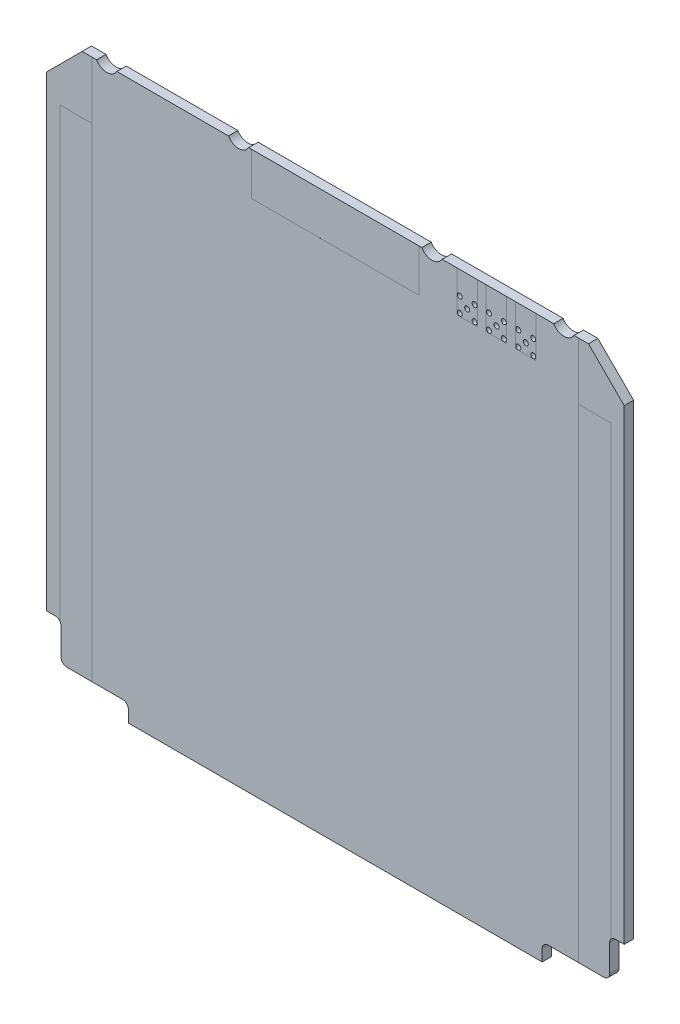
SolidWorks part; units mm, degrees
material "FR4_stuffedProtoboard"
ref_plane "Front Plane" through (0, 0, 0) normal (0, 0, 1) x (1, 0, 0)
ref_plane "Top Plane" through (0, 0, 0) normal (0, 1, 0) x (1, 0, 0)
ref_plane "Right Plane" through (0, 0, 0) normal (1, 0, 0) x (0, 0, -1)
ref_plane "Plane4" through (0, 0, -0.0125) normal (0, 0, -1) x (-1, 0, 0)
sketch "Sketch1" plane through (0, 0, -0.0125) normal (0, 0, -1) x (-1, 0, 0)
  line L4 (49.3, -50) -> (49.3, 45.3)
  line L6 (49.3, 45.3) -> (-49.3, 45.3)
  line L12 (-49.3, 45.3) -> (-49.3, -50)
  line L17 (-49.3, -50) -> (49.3, -50)
  line L18 (0, -50) -> (0, 45.3) construction
  dimension "D7" = 95.3
  dimension "D1" = 98.6
  dimension "D34" = 50
extrude "basicSize" add sketch "Sketch1" against normal blind 1.6
chamfer "Chamfer1" distance 6.1 angle 45 2 edges at (49.3, 45.3, 0.7875) (-49.3, 45.3, 0.7875)
sketch "Sketch4" plane through (0, 0, 1.5875) normal (0, 0, 1) x (1, 0, 0)
  line L1 (37.2679, 45.3) -> (40.7321, 45.3)
  line L7 (-43.2, 45.3) -> (43.2, 45.3) construction
  line L8 (49.3, 39.2) -> (49.3, -50) construction
  arc A0 (40.7321, 45.3) -> (37.2679, 45.3) centre (39, 46.3) cw
  point P5 (39, 44.3)
  dimension "D1" = 2
  dimension "D3" = 10.3
  dimension "D2" = 1
extrude "backplaneSideScrewCutout" cut sketch "Sketch4" against normal through all both and the other way through all
pattern_linear "LPattern3" count 2 spacing 22.5 along (-1, 0, 0) of "backplaneSideScrewCutout"
mirror "Mirror3" about plane through (0, 0, 0) normal (1, 0, 0) of "LPattern3"
sketch "Sketch6" plane through (0, 0, 1.5875) normal (0, 0, 1) x (1, 0, 0)
  line L0 (-49.3, -50) -> (-49.3, 39.2) construction
  line L1 (-49.3, -40.4) -> (-46.8, -40.4)
  line L2 (-49.3, -40.4) -> (-49.3, -50)
  line L4 (-46.8, -40.4) -> (-46.8, -47)
  line L5 (49.3, -50) -> (-49.3, -50) construction
  line L6 (-35.3, -50) -> (-49.3, -50)
  line L7 (-35.3, -50) -> (-35.3, -47)
  line L8 (-35.3, -47) -> (-46.8, -47)
  dimension "D1" = 2.5
  dimension "D2" = 3
  dimension "D3" = 9.6
  dimension "D4" = 14
extrude "Cut-Extrude4" cut sketch "Sketch6" against normal through all
fillet "Fillet1" radius 1 3 edges at (-35.3, -47, 0.7875) (-46.8, -47, 0.7875) (-46.8, -40.4, 0.7875)
mirror "Mirror1" about plane through (0, 0, 0) normal (1, 0, 0) of "Cut-Extrude4", "Fillet1"
sketch "Sketch5" plane through (0, 0, 1.5875) normal (0, 0, 1) x (1, 0, 0)
  line L0 (21.23, 41.37) -> (23.77, 38.83) construction
  line L1 (21.23, 38.83) -> (21.23, 41.37) construction
  line L2 (21.23, 41.37) -> (23.77, 41.37) construction
  line L4 (49.3, 39.2) -> (49.3, -40.4) construction
  line L5 (-14.7679, 45.3) -> (14.7679, 45.3) construction
  circle A0 centre (22.5, 40.1) radius 0.425
  circle A1 centre (21.23, 41.37) radius 0.425
  circle A3 centre (21.23, 38.83) radius 0.425
  circle A4 centre (23.77, 41.37) radius 0.425
  circle A5 centre (23.77, 38.83) radius 0.425
  dimension "D2" = 0.85
  dimension "D1" = 2.54
  dimension "D3" = 3.93
  dimension "D4" = 28.07
extrude "Cut-Extrude3" cut sketch "Sketch5" against normal through all
pattern_linear "LPattern2" count 3 spacing 5 along (1, 0, 0) of "Cut-Extrude3"
sketch "partFootprints" plane through (0, 0, 1.5875) normal (0, 0, 1) x (1, 0, 0)
  line L1 (18.2321, 45.3) -> (37.2679, 45.3) construction
  line L6 (20.75, 45.3) -> (20.75, 38.35)
  line L7 (20.75, 38.35) -> (24.25, 38.35)
  line L8 (24.25, 38.35) -> (24.25, 45.3)
  line L9 (24.25, 45.3) -> (20.75, 45.3)
  line L10 (25.75, 45.3) -> (25.75, 38.35)
  line L11 (25.75, 38.35) -> (29.25, 38.35)
  line L12 (29.25, 38.35) -> (29.25, 45.3)
  line L13 (29.25, 45.3) -> (25.75, 45.3)
  line L14 (30.75, 45.3) -> (30.75, 38.35)
  line L15 (30.75, 38.35) -> (34.25, 38.35)
  line L16 (34.25, 38.35) -> (34.25, 45.3)
  line L17 (34.25, 45.3) -> (30.75, 45.3)
  line L19 (32.5, 38.35) -> (32.5, 40.1) construction
  line L23 (22.5, 38.35) -> (22.5, 40.1) construction
  circle A2 centre (22.5, 40.1) radius 0.425 construction
  circle A5 centre (32.5, 40.1) radius 0.425 construction
  dimension "D1" = 1.75
  dimension "D8" = 3.5
  dimension "D6" = 3
extrude "MMCXfootprint" cut sketch "partFootprints" against normal blind 0.0001
sketch "Sketch7" plane through (0, 0, 1.5875) normal (0, 0, 1) x (1, 0, 0)
  line L0 (-14.2875, 45.5) -> (-14.2875, 39.912) construction
  line L1 (-14.2875, 45.3) -> (-14.2875, 38.007)
  line L2 (-12.2428, 38.007) -> (-11.8872, 38.007) construction
  line L3 (-14.2875, 38.007) -> (14.2875, 38.007)
  line L4 (14.2875, 45.5) -> (14.2875, 39.912) construction
  line L5 (14.2875, 45.3) -> (14.2875, 38.007)
  line L7 (-14.7679, 45.3) -> (14.7679, 45.3) construction
  line L8 (-14.2875, 45.3) -> (14.2875, 45.3)
extrude "TigerEyeFootprint" cut sketch "Sketch7" against normal blind 0.0001
sketch "thermalContacts_upper" plane through (0, 0, 1.5875) normal (0, 0, 1) x (1, 0, 0)
  line L0 (-49.3, -40.4) -> (-49.3, 39.2) construction
  line L1 (35.3, -50) -> (-35.3, -50) construction
  line L2 (-49.3, 45.3) -> (49.3, 45.3) construction
  line L3 (-47, 35.5) -> (-47, -41.5)
  line L5 (-41.5, 35.5) -> (-47, 35.5)
  line L18 (-41.5, 35.5) -> (-41.5, 47)
  line L23 (-41.5, 47) -> (-56.1922, 47)
  line L24 (-56.1922, 47) -> (-56.1922, -41.5)
  line L25 (-56.1922, -41.5) -> (-47, -41.5)
  dimension "D1" = 2.3
  dimension "D2" = 8.5
  dimension "D3" = 9.8
  dimension "D4" = 7.8
  dimension "D5" = 88.5
  dimension "D6" = 14.6922
extrude "keepOut_bottom" cut sketch "thermalContacts_upper" against normal blind 0.0001
sketch "Sketch3" plane through (0, 0, 1.5875) normal (0, 0, 1) x (1, 0, 0)
  line L0 (18.2321, 45.3) -> (20.75, 45.3) construction
  line L1 (-46.8, -46) -> (-46.8, -41.4) construction
  line L2 (-36.3, -47) -> (-45.8, -47) construction
  line L3 (-47, -40.8) -> (-47, 35.5) construction
  line L10 (0, -50) -> (0, 45.3) construction
  line L11 (35.3, -50) -> (-35.3, -50) construction
  line L13 (-41.5, 35.5) -> (-47, 35.5)
  line L14 (-45.8, -47) -> (-41.5, -47)
  line L15 (-46.8, -41.4) -> (-46.8, -46)
  line L16 (-47, 35.5) -> (-47, -40.8)
  line L17 (-41.5, -47) -> (-41.5, 35.5)
  arc A2 (-46.8, -41.4) -> (-47, -40.8) centre (-47.8, -41.4) ccw construction
  arc A3 (-46.8, -46) -> (-45.8, -47) centre (-45.8, -46) ccw construction
  arc A4 (-45.8, -47) -> (-46.8, -46) centre (-45.8, -46) cw
  arc A5 (-47, -40.8) -> (-46.8, -41.4) centre (-47.8, -41.4) cw
extrude "caution_top" cut sketch "Sketch3" against normal blind 0.0001
ref_plane "midplane_Z" through (0, 0, 0.7875) normal (0, 0, 1) x (1, 0, 0)
mirror "clearances_top-bottom" about plane through (0, 0, 0.7875) normal (0, 0, 1) of "keepOut_bottom", "caution_top"
mirror "clearances_side-side" about plane through (0, 0, 0) normal (1, 0, 0) of "clearances_top-bottom"
ref_point "rail midpoint"
sketch "locatorSketch" plane through (0, 0, 1.5875) normal (0, 0, 1) x (1, 0, 0)
  line L0 (-12.2428, 39.531) -> (12.2428, 38.007) construction
  line L1 (12.2428, 39.531) -> (-12.2428, 38.007) construction
  line L4 (-12.2428, 38.261) -> (-12.2428, 38.007)
  line L5 (-11.8872, 38.261) -> (-12.2428, 38.261)
  line L6 (-11.8872, 38.007) -> (-11.8872, 38.261)
  line L7 (-12.2428, 38.007) -> (-11.8872, 38.007)
  line L8 (-12.2428, 38.261) -> (-12.2428, 38.007)
  line L9 (-11.8872, 38.261) -> (-12.2428, 38.261)
  line L10 (-11.8872, 38.007) -> (-11.8872, 38.261)
  line L11 (-12.2428, 38.007) -> (-11.8872, 38.007)
  line L12 (-12.2428, 39.531) -> (-12.2428, 39.277)
  line L13 (-11.8872, 39.531) -> (-12.2428, 39.531)
  line L14 (-11.8872, 39.277) -> (-11.8872, 39.531)
  line L15 (-12.2428, 39.277) -> (-11.8872, 39.277)
  line L16 (-12.2428, 39.531) -> (-12.2428, 39.277)
  line L17 (-11.8872, 39.531) -> (-12.2428, 39.531)
  line L18 (-11.8872, 39.277) -> (-11.8872, 39.531)
  line L19 (-12.2428, 39.277) -> (-11.8872, 39.277)
  line L20 (11.8872, 39.531) -> (11.8872, 39.277)
  line L21 (12.2428, 39.531) -> (11.8872, 39.531)
  line L22 (12.2428, 39.277) -> (12.2428, 39.531)
  line L23 (11.8872, 39.277) -> (12.2428, 39.277)
  line L24 (11.8872, 39.531) -> (11.8872, 39.277)
  line L25 (12.2428, 39.531) -> (11.8872, 39.531)
  line L26 (12.2428, 39.277) -> (12.2428, 39.531)
  line L27 (11.8872, 39.277) -> (12.2428, 39.277)
  line L28 (11.8872, 38.261) -> (11.8872, 38.007)
  line L29 (12.2428, 38.261) -> (11.8872, 38.261)
  line L30 (12.2428, 38.007) -> (12.2428, 38.261)
  line L31 (11.8872, 38.007) -> (12.2428, 38.007)
  line L32 (11.8872, 38.261) -> (11.8872, 38.007)
  line L33 (12.2428, 38.261) -> (11.8872, 38.261)
  line L34 (12.2428, 38.007) -> (12.2428, 38.261)
  line L35 (11.8872, 38.007) -> (12.2428, 38.007)
  dimension "D1" = 0
  dimension "D2" = 0
  dimension "D3" = 0
  dimension "D4" = 0
